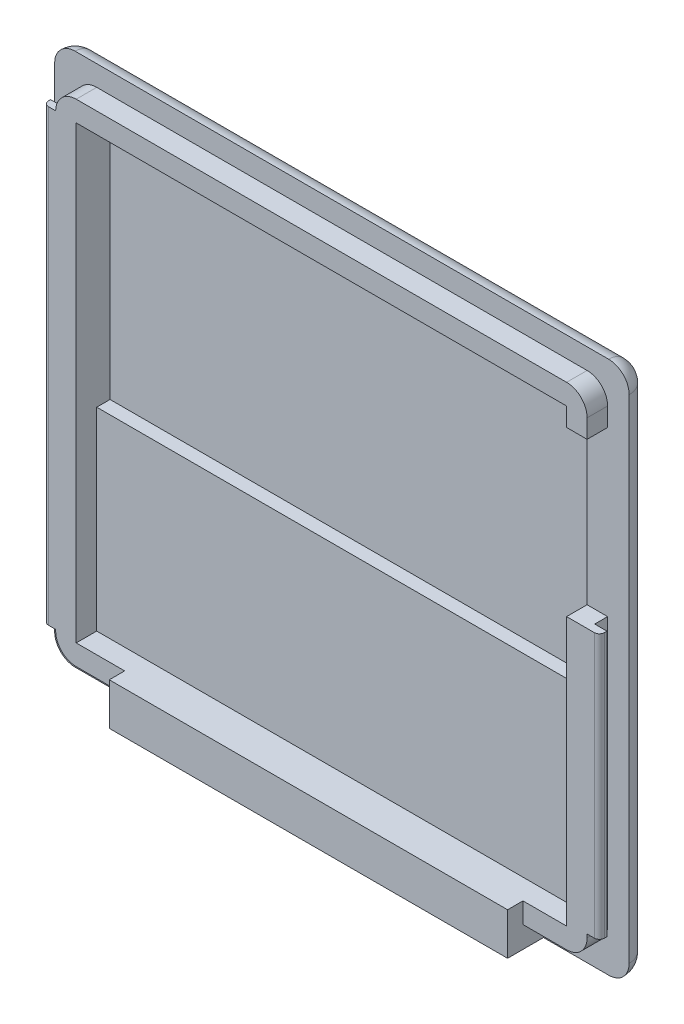
SolidWorks part; units mm, degrees
ref_plane "前视基准面" through (0, 0, 0) normal (0, 0, 1) x (1, 0, 0)
ref_plane "上视基准面" through (0, 0, 0) normal (0, 1, 0) x (1, 0, 0)
ref_plane "右视基准面" through (0, 0, 0) normal (1, 0, 0) x (0, 0, -1)
sketch "草图1" plane through (0, 0, 0) normal (0, 0, 1) x (1, 0, 0)
  line L0 (-38.0301, 26.7577) -> (-38.0301, 28.7077)
  line L1 (-38.0301, 26.7577) -> (13.9699, 26.7577)
  line L2 (-38.0301, 26.7577) -> (-38.0301, -21.2923)
  line L3 (-38.0301, -21.2923) -> (13.9699, -21.2923)
  line L4 (13.9699, 26.7577) -> (13.9699, -21.2923)
  line L5 (-38.0301, 28.7077) -> (-40.0301, 28.7077)
  line L6 (13.9699, -21.2923) -> (15.9699, -21.2923)
  line L7 (15.9699, -21.2923) -> (15.9699, -23.2923)
  line L9 (-40.0301, 28.7077) -> (15.9699, 28.7077)
  line L10 (-40.0301, 28.7077) -> (-40.0301, -23.2923)
  line L11 (-40.0301, -23.2923) -> (15.9699, -23.2923)
  line L12 (15.9699, 28.7077) -> (15.9699, -23.2923)
  dimension "D1" = 48.05
  dimension "D2" = 52
extrude "凸台-拉伸1" add sketch "草图1" along normal blind 2 contours L10 L11 L7 L6 L3 L2 L0 L5 | L12 L9 L0 L1 L4 L6 | L4 L1 L2 L3 region at (-38.7943, 2.7327, 0) region at (-37.2942, 27.7327, 0) region at (-12.0301, 2.7327, 0)
sketch "草图2" plane through (0, 0, 2) normal (0, 0, 1) x (1, 0, 0)
  line L0 (-38.1655, 28.7077) -> (-38.1655, 26.7677)
  line L1 (15.9699, 28.7077) -> (-40.0301, 28.7077) construction
  line L2 (12.7339, -23.2923) -> (12.7339, -21.1923)
  line L3 (-40.0301, 28.7077) -> (-40.0301, -23.2923) construction
  line L4 (-40.0301, 25.7989) -> (-37.9301, 25.7989)
  line L5 (-37.225, 28.7077) -> (-37.225, 26.7077)
  line L6 (-40.0301, -23.2923) -> (15.9699, -23.2923) construction
  line L7 (15.9699, -20.4802) -> (13.8699, -20.4802)
  line L8 (15.9699, 28.7077) -> (15.9699, -23.2923) construction
  line L10 (13.8699, -21.1923) -> (-37.9301, -21.1923)
  line L11 (13.8699, -21.1923) -> (13.8699, 26.7677)
  line L13 (-37.9301, -21.1923) -> (-37.9301, 26.7677)
  line L14 (13.8699, -21.1923) -> (-37.9301, -21.1923)
  line L15 (13.8699, -21.1923) -> (13.8699, 26.7077)
  line L16 (13.8699, 26.7077) -> (-37.9301, 26.7077)
  line L17 (-37.9301, -21.1923) -> (-37.9301, 26.7077)
extrude "凸台-拉伸2" add sketch "草图2" along normal blind 2 contours L11 L16 L13 L10 | L15 L14 L17 L16 region at (-12.0301, 2.7577, 2)
sketch "草图3" plane through (0, 0, 4) normal (0, 0, 1) x (1, 0, 0)
  line L0 (-37.9301, 26.7077) -> (-37.9301, 24.7077)
  line L1 (-37.9301, -21.1923) -> (-37.9301, 26.7077) construction
  line L2 (-37.9301, 24.7077) -> (-35.9301, 24.7077)
  line L3 (13.8699, -21.1923) -> (13.8699, -19.1923)
  line L4 (13.8699, -21.1923) -> (13.8699, 26.7077) construction
  line L5 (13.8699, -21.1923) -> (13.8699, 26.7077) construction
  line L6 (13.8699, -19.1923) -> (11.8699, -19.1923)
  line L8 (11.8699, -19.1923) -> (-35.9301, -19.1923)
  line L9 (11.8699, -19.1923) -> (11.8699, 24.7077)
  line L10 (11.8699, 24.7077) -> (-35.9301, 24.7077)
  line L11 (-35.9301, -19.1923) -> (-35.9301, 24.7077)
extrude "切除-拉伸1" cut sketch "草图3" against normal blind 2 contours L11 L8 L9 L10 region at (-12.0301, 2.7577, 4)
sketch "草图4" plane through (0, 0, 4) normal (0, 0, 1) x (1, 0, 0)
  line L0 (11.8699, -19.1923) -> (11.8699, 24.7077) construction
  line L1 (11.8699, 22.8946) -> (13.8699, 22.8946)
  line L2 (11.8699, 22.8946) -> (11.8699, 9.8269)
  line L3 (11.8699, 9.8269) -> (13.8699, 9.8269)
  line L4 (13.8699, 22.8946) -> (13.8699, 9.8269)
  line L5 (13.8699, -21.1923) -> (13.8699, 26.7077) construction
  line L7 (11.8699, 22.8946) -> (13.8699, 22.8946)
  line L8 (11.8699, 22.8946) -> (11.8699, 6.9306)
  line L9 (11.8699, 6.9306) -> (13.8699, 6.9306)
  line L10 (13.8699, 22.8946) -> (13.8699, 6.9306)
  line M5 (13.8699, -21.1923) -> (13.8699, 26.7077)
  line M12 (11.8699, 24.7077) -> (11.8699, -19.1923)
extrude "切除-拉伸2" cut sketch "草图4" against normal blind 2 contours L3 L1 M12 M5 | L9 L3 M12 M5 region at (12.8699, 16.3607, 4) region at (12.8699, 8.3787, 4)
fillet "圆角2" radius 2 4 edges at (-12.0301, 28.7077, 0) (15.9699, 2.7077, 0) (-40.0301, 2.7077, 0) (-12.0301, -23.2923, 0)
sketch "草图5" plane through (0, 0, 2) normal (0, 0, 1) x (1, 0, 0)
  line L0 (-35.9301, 24.7077) -> (-35.9301, -0.2923)
  line L1 (-35.9301, -19.1923) -> (-35.9301, 24.7077) construction
  line L2 (-35.9301, -0.2923) -> (11.8699, -0.2923)
  line L3 (11.8699, -19.1923) -> (11.8699, 6.9306) construction
  line L5 (-35.9301, 24.7077) -> (11.8699, 24.7077)
  line L6 (-35.9301, 24.7077) -> (-35.9301, -0.2923)
  line L7 (-35.9301, -0.2923) -> (11.8699, -0.2923)
  line L8 (11.8699, 24.7077) -> (11.8699, -0.2923)
  line M7 (11.8699, 22.8946) -> (11.8699, 24.7077)
  line M8 (11.8699, 24.7077) -> (-35.9301, 24.7077)
  line M9 (-35.9301, 24.7077) -> (-35.9301, -19.1923)
  line M11 (11.8699, -19.1923) -> (11.8699, 6.9306)
extrude "切除-拉伸3" cut sketch "草图5" against normal blind 2 contours L8 L2 M7 M8 M9 M11 region at (-12.0301, 12.2077, 2)
sketch "草图6" plane through (0, 0, 0) normal (0, 0, 1) x (1, 0, 0)
  line L0 (-35.9301, 24.7077) -> (-35.9301, -0.2923)
  line L2 (-35.9301, -0.2923) -> (11.8699, -0.2923)
  line L5 (-35.9301, 24.7077) -> (11.8699, 24.7077)
  line L6 (-35.9301, 24.7077) -> (-35.9301, -0.2923)
  line L7 (-35.9301, -0.2923) -> (11.8699, -0.2923)
  line L8 (11.8699, 24.7077) -> (11.8699, -0.2923)
extrude "凸台-拉伸3" add sketch "草图6" along normal blind 0.7 contours L8 L5 L0 L2 region at (-12.0301, 12.2077, 0)
sketch "草图7" plane through (0, 0, 0) normal (0, 0, 1) x (1, 0, 0)
  line L0 (-35.9301, 24.7077) -> (-35.9301, -0.2923)
  line L2 (-35.9301, -0.2923) -> (11.8699, -0.2923)
  line L5 (-35.9301, 24.7077) -> (11.8699, 24.7077)
  line L6 (-35.9301, 24.7077) -> (-35.9301, -0.2923)
  line L7 (-35.9301, -0.2923) -> (11.8699, -0.2923)
  line L8 (11.8699, 24.7077) -> (11.8699, -0.2923)
extrude "切除-拉伸4" cut sketch "草图7" along normal blind 0.01 contours L8 L5 L0 L2 region at (-12.0301, 12.2077, 0)
sketch "草图8" plane through (0, 0, 0) normal (0, 0, -1) x (-1, 0, 0)
  text T0 "1-12PIN GND EXT_T" font "Century Gothic" height in points 14
  text T1 "<b>logicAnalyzer</b>" font "Comic Sans MS" height in points 18
extrude "切除-拉伸5" cut sketch "草图8" against normal blind 0.01
sketch "草图9" plane through (-37.9301, 0, 0) normal (-1, 0, 0) x (0, 0, 1)
  line L0 (2, 16.2552) -> (3.3, 16.2552)
  line L1 (2, -21.1923) -> (2, 26.7077) construction
  line L2 (4, -21.1923) -> (4, 26.7077) construction
  line L3 (4, 24.7224) -> (3.3, 24.7224)
  line L4 (4, 24.7224) -> (4, -19.0516)
  line L5 (4, -19.0516) -> (3.3, -19.0516)
  line L6 (3.3, 24.7224) -> (3.3, -19.0516)
  line M3 (4, -21.1923) -> (4, 26.7077)
extrude "凸台-拉伸4" add sketch "草图9" along normal blind 1.2 contours L3 L6 L5 M3 region at (-37.9301, 2.8354, 3.65)
sketch "草图10" plane through (13.8699, 0, 0) normal (1, 0, 0) x (0, 0, -1)
  line L0 (-2, 7.6607) -> (-3.26, 7.6607)
  line L1 (-2, -21.1923) -> (-2, 6.9306) construction
  line L2 (-2, 9.8108) -> (-4, 9.8108) construction
  line L3 (-3.26, 9.8108) -> (-4, 9.8108)
  line L4 (-3.26, 9.8108) -> (-3.26, -18.8613)
  line L5 (-3.26, -18.8613) -> (-4, -18.8613)
  line L6 (-4, 9.8108) -> (-4, -18.8613)
  line L7 (-4, -21.1923) -> (-4, 6.9306) construction
  line L9 (-3.26, -18.8613) -> (-4, -18.8613)
  line L10 (-3.26, -18.8613) -> (-3.26, 6.9306)
  line L11 (-3.26, 6.9306) -> (-4, 6.9306)
  line L12 (-4, -18.8613) -> (-4, 6.9306)
extrude "凸台-拉伸5" add sketch "草图10" along normal blind 1.2 contours L10 L9 L12 L11
sketch "草图11" plane through (0, 0, 2) normal (0, 0, 1) x (1, 0, 0)
  line L0 (-40.0301, -21.2923) -> (-40.0301, -24.6427)
  line L1 (-40.0301, 26.7077) -> (-40.0301, -21.2923) construction
  line L2 (-36.4282, -23.2923) -> (-40.0301, -23.2923)
  line L3 (-38.0301, -23.2923) -> (13.9699, -23.2923) construction
  line L4 (-40.0301, -23.2923) -> (-31.0301, -23.2923)
  line L5 (-40.0301, -23.2923) -> (-31.0301, -23.2923)
  line L6 (15.9699, -21.2923) -> (15.9699, -23.2923)
  line L7 (15.9699, -23.2923) -> (8.9699, -23.2923)
  line L8 (11.8699, -19.1923) -> (-35.9301, -19.1923) construction
  line L13 (-29.6973, -23.2923) -> (-31.2061, -23.2923)
  line L18 (-31.2061, -23.2923) -> (-31.2061, -19.1923)
  line L20 (-31.2061, -23.2923) -> (7.6182, -23.2923)
  line L21 (-31.2061, -23.2923) -> (-31.2061, -19.1923)
  line L22 (-31.2061, -19.1923) -> (7.6182, -19.1923)
  line L23 (7.6182, -23.2923) -> (7.6182, -19.1923)
  arc A0 (-40.0301, -21.2923) -> (-38.0301, -23.2923) centre (-38.0301, -21.2923) ccw construction
  line M3 (-38.0301, -23.2923) -> (13.9699, -23.2923)
  line M13 (13.8699, -21.1923) -> (-37.9301, -21.1923)
extrude "凸台-拉伸6" add sketch "草图11" along normal blind 3.5 contours L23 L18 L5 M3 M13 | L23 L22 L18 M13 region at (-11.7939, -22.2423, 2) region at (-11.7939, -20.1923, 2)
fillet "圆角3" radius 0.5 2 edges at (-39.1301, 2.8354, 4) (15.0699, -5.9653, 4)
fillet "圆角4" radius 2 4 edges at (-37.9301, 26.7077, 3) (13.8699, 26.7077, 3) (13.8699, -21.1923, 3) (-37.9301, -21.1923, 3)
